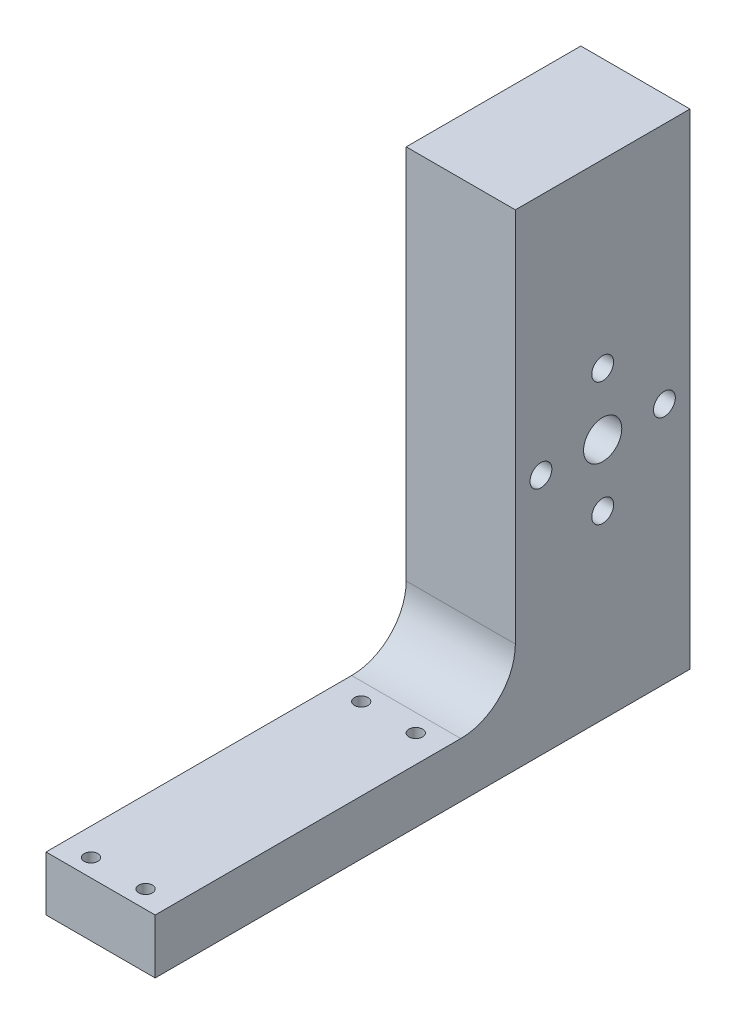
SolidWorks part; units mm, degrees
ref_plane "Front" through (0, 0, 0) normal (0, 0, 1) x (1, 0, 0)
ref_plane "Top" through (0, 0, 0) normal (0, 1, 0) x (1, 0, 0)
ref_plane "Right" through (0, 0, 0) normal (1, 0, 0) x (0, 0, -1)
sketch "Sketch1" plane through (0, 0, 0) normal (0, 1, 0) x (1, 0, 0)
  line L0 (0, 44) -> (20, 44)
  line L1 (0, 0) -> (20, 0)
  line L2 (0, 0) -> (0, 44)
  line L3 (0, 44) -> (20, 44)
  line L4 (20, 0) -> (20, 44)
  line L5 (0, 44) -> (0, 60)
  line L6 (20, 44) -> (20, 60)
  line L7 (0, 60) -> (20, 60)
  line L8 (20, 0) -> (0, 0)
  line L9 (20, 0) -> (20, -6)
  line L10 (0, 0) -> (0, -6)
  line L11 (20, -6) -> (0, -6)
  line L12 (0, 22) -> (20, 22)
  line L13 (10, -2.75) -> (10, 46.75)
  line L14 (5, -2.75) -> (15, -2.75)
  line L15 (5, 46.75) -> (15, 46.75)
  circle A0 centre (5, -2.75) radius 1.25
  circle A1 centre (15, -2.75) radius 1.25
  circle A2 centre (5, 46.75) radius 1.25
  circle A3 centre (15, 46.75) radius 1.25
  point P14 (10, 22)
  point P17 (10, -2.75)
  point P20 (10, 46.75)
  dimension "D1" = 44
  dimension "D2" = 20
  dimension "D3" = 6
  dimension "D4" = 16
  dimension "D5" = 49.5
extrude "Boss-Extrude1" add sketch "Sketch1" along normal blind 10 contours L1 L13 L12 L2 | A1 A0 L1 L10 L11 L9 L8 | L13 L8 L4 L12 | L13 L12 L4 L3 | L12 L13 L0 L2 | A3 L3 L6 L7 L5 L0 A2 region at (10, 0, -52.1662) region at (5, 0, -33) region at (15, 0, -33) region at (5, 0, -11) region at (15, 0, -11) region at (10, 0, 3.0223)
sketch "Sketch2" plane through (0, 0, -60) normal (0, 0, -1) x (-1, 0, 0)
  line L0 (-20, 0) -> (0, 0)
  line L1 (-20, 0) -> (-20, 88.9)
  line L2 (0, 0) -> (0, 88.9)
  line L3 (-20, 88.9) -> (0, 88.9)
  dimension "D1" = 88.9
extrude "Boss-Extrude2" add sketch "Sketch2" along normal blind 32
fillet "Fillet1" radius 10 1 edges at (10, 10, -60)
sketch "Sketch3" plane through (20, 0, 0) normal (1, 0, 0) x (0, 0, -1)
  line L0 (76, 88.9) -> (76, 0)
  line L1 (92, 88.9) -> (60, 88.9) construction
  line L2 (-6, 0) -> (92, 0) construction
  circle A0 centre (76, 44.45) radius 11.3137
  circle A1 centre (76, 33.1363) radius 2
  circle A2 centre (87.3137, 44.45) radius 2
  circle A3 centre (64.6863, 44.45) radius 2
  circle A4 centre (76, 55.7637) radius 2
  circle A5 centre (76, 44.45) radius 3.5
extrude "Cut-Extrude1" cut sketch "Sketch3" against normal blind 32 contours L0 A5 | L0 A5 | A0 A2 | A0 A2 | A1 | A3 | A4 region at (20, 44.45, -77.4854) region at (20, 44.45, -74.5146) region at (20, 44.45, -88.1299) region at (20, 44.45, -86.4338)
